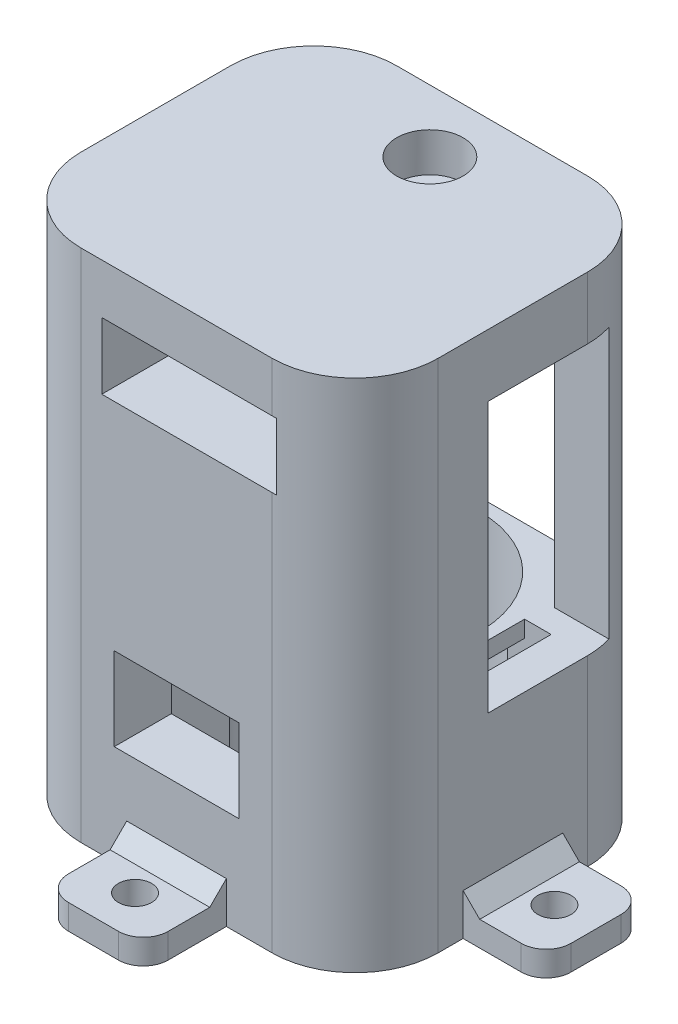
SolidWorks part; units mm, degrees
ref_plane "Plano frontal" through (0, 0, 0) normal (0, 0, 1) x (1, 0, 0)
ref_plane "Plano superior" through (0, 0, 0) normal (0, 1, 0) x (1, 0, 0)
ref_plane "Plano direito" through (0, 0, 0) normal (1, 0, 0) x (0, 0, -1)
sketch "Esboço2" plane through (0, 0, 0) normal (0, 1, 0) x (1, 0, 0)
  line L1 (0, 0) -> (43, 0)
  line L2 (0, 0) -> (0, 38)
  line L3 (0, 38) -> (43, 38)
  line L4 (43, 0) -> (43, 38)
  dimension "D1" = 43
  dimension "D2" = 38
extrude "Base" add sketch "Esboço2" along normal blind 22
sketch "Esboço3" plane through (0, 0, 0) normal (0, 1, 0) x (1, 0, 0)
  line L0 (21.5, -2.1425) -> (21.5, 46.202) construction
  line L1 (-2.8555, 24) -> (47.4642, 24) construction
  line L2 (43, 0) -> (43, 38) construction
  line L3 (43, 38) -> (0, 38) construction
  line L5 (12, 6.876) -> (31, 6.876)
  line L6 (12, 6.876) -> (12, 15.876)
  line L7 (12, 15.876) -> (31, 15.876)
  line L8 (31, 6.876) -> (31, 15.876)
  line L9 (12, 6.876) -> (31, 15.876) construction
  line L10 (12, 15.876) -> (31, 6.876) construction
  circle A0 centre (21.5, 24) radius 12.5
  point P10 (21.5, 11.376)
  point P15 (0, 0)
  point P16 (0, 0)
  dimension "D1" = 25
  dimension "D2" = 21.5
  dimension "D3" = 14
  dimension "D4" = 19
  dimension "D5" = 9
extrude "Corte do encaixe do motor" cut sketch "Esboço3" along normal through all contours A0 L8 L7 L6 | A0 L6 L7 L8 | L6 A0 L8 L5 region at (21.5, 0, -9.99) region at (21.5, 0, -25.3196) region at (21.5, 0, -14.0963)
sketch "Esboço5" plane through (0, 22, 0) normal (0, 1, 0) x (1, 0, 0)
  line L0 (42.9706, 24) -> (-2.5153, 24) construction
  line L1 (21.5, 41.517) -> (21.5, 6.483) construction
  line L3 (4.4, 28) -> (7.6, 28)
  line L4 (4.4, 28) -> (4.4, 20)
  line L5 (4.4, 20) -> (7.6, 20)
  line L6 (7.6, 28) -> (7.6, 20)
  line L7 (4.4, 28) -> (7.6, 20) construction
  line L8 (4.4, 20) -> (7.6, 28) construction
  line L9 (35.4, 28) -> (38.6, 28)
  line L10 (35.4, 28) -> (35.4, 20)
  line L11 (35.4, 20) -> (38.6, 20)
  line L12 (38.6, 28) -> (38.6, 20)
  line L13 (35.4, 28) -> (38.6, 20) construction
  line L14 (35.4, 20) -> (38.6, 28) construction
  point P3 (6, 24)
  point P10 (21.5, 24)
  point P11 (37, 24)
  dimension "D1" = 8
  dimension "D2" = 3.2
  dimension "D3" = 8
  dimension "D4" = 3.2
  dimension "D5" = 15.5
  dimension "D6" = 15.5
extrude "Corte dos parafusos do motor" cut sketch "Esboço5" against normal through all
sketch "Esboço10" plane through (0, 22, 0) normal (0, 1, 0) x (1, 0, 0)
  line L0 (43, 0) -> (43, 38) construction
  line L1 (0, 38) -> (7, 38)
  line L2 (0, 38) -> (0, 31)
  line L3 (0, 31) -> (7, 31)
  line L4 (7, 38) -> (7, 31)
  line L5 (43, 38) -> (36, 38)
  line L6 (43, 38) -> (43, 31)
  line L7 (43, 31) -> (36, 31)
  line L8 (36, 38) -> (36, 31)
  line L9 (0, 0) -> (43, 0)
  line L10 (0, 0) -> (0, 5.5)
  line L11 (0, 5.5) -> (43, 5.5)
  line L12 (43, 0) -> (43, 5.5)
  line L14 (0, 5.5) -> (7, 5.5)
  line L15 (0, 5.5) -> (0, 16)
  line L16 (0, 16) -> (7, 16)
  line L17 (7, 5.5) -> (7, 16)
  line L18 (43, 5.5) -> (36, 5.5)
  line L19 (43, 5.5) -> (43, 16)
  line L20 (43, 16) -> (36, 16)
  line L21 (36, 5.5) -> (36, 16)
  line M13 (31, 6.876) -> (12, 6.876)
  line M15 (0, 0) -> (43, 0)
  line M16 (43, 0) -> (43, 38)
  line M17 (43, 38) -> (0, 38)
  line M18 (0, 38) -> (0, 0)
  dimension "D1" = 5.5
  dimension "D2" = 7
  dimension "D3" = 7
  dimension "D4" = 7
  dimension "D5" = 7
  dimension "D6" = 7
  dimension "D7" = 7
  dimension "D8" = 10.5
  dimension "D9" = 10.5
extrude "Base extendida" add sketch "Esboço10" along normal blind 35 contours L11 M18 M15 M16 M13 | L21 L11 L20 M16 | L8 L7 M17 M16 | L11 L17 L16 M18 | L4 L3 M17 M18 region at (3.5, 22, -34.5) region at (39.5, 22, -34.5) region at (3.5, 22, -10.75) region at (21.5, 22, -2.75) region at (39.5, 22, -10.75)
sketch "Esboço11" plane through (7, 0, 0) normal (1, 0, 0) x (0, 0, -1)
  line L0 (16, 57) -> (16, 47)
  line L1 (16, 57) -> (16, 22) construction
  line L2 (16, 57) -> (5.5, 57)
  line L3 (5.5, 57) -> (16, 57) construction
  line L4 (5.5, 57) -> (5.5, 32.0044)
  line L5 (16, 47) -> (5.5, 32.0044)
  dimension "D1" = 10.5
  dimension "D2" = 35
  dimension "D3" = 10
extrude "Chanfro da base extendida" add sketch "Esboço11" along normal through all
sketch "Esboço12" plane through (0, 0, -16) normal (0, 0, -1) x (-1, 0, 0)
  line L1 (-43, 57) -> (-36, 57)
  line L2 (-43, 57) -> (-43, 54.5)
  line L3 (-43, 54.5) -> (-36, 54.5)
  line L4 (-36, 57) -> (-36, 54.5)
  dimension "D1" = 2.5
  dimension "D2" = 7
extrude "Ponte 1" add sketch "Esboço12" along normal through all
sketch "Esboço13" plane through (0, 0, -16) normal (0, 0, -1) x (-1, 0, 0)
  line L1 (0, 57) -> (-7, 57)
  line L2 (0, 57) -> (0, 54.5)
  line L3 (0, 54.5) -> (-7, 54.5)
  line L4 (-7, 57) -> (-7, 54.5)
  dimension "D1" = 2.5
  dimension "D2" = 7
extrude "Ponte 2" add sketch "Esboço13" along normal through all
sketch "Esboço14" plane through (0, 57, 0) normal (0, 1, 0) x (1, 0, 0)
  line L1 (0, 0) -> (43, 0)
  line L2 (0, 0) -> (0, 38)
  line L3 (0, 38) -> (43, 38)
  line L4 (43, 0) -> (43, 38)
extrude "Telhado" add sketch "Esboço14" along normal blind 5
sketch "Esboço18" plane through (0, 62, 0) normal (0, 1, 0) x (1, 0, 0)
  line L0 (21.5, 37.438) -> (21.5, -2.8891) construction
  line L1 (43, 0) -> (43, 38) construction
  line L2 (43, 38) -> (0, 38) construction
  circle A0 centre (21.5, 30.5) radius 4
  dimension "D2" = 8
  dimension "D3" = 7.5
  dimension "D1" = 21.5
extrude "Furo do Eixo" cut sketch "Esboço18" against normal blind 8
sketch "Esboço23" plane through (0, 57, 0) normal (0, -1, 0) x (1, 0, 0)
  line L0 (36, -30.4716) -> (22.9081, -16)
  line L1 (7, -30.4716) -> (17.2307, -16)
  line L2 (36, -16) -> (36, -30.4716)
  line L3 (36, -38) -> (36, -16) construction
  line L4 (7, -16) -> (36, -16) construction
  line L5 (22.9081, -16) -> (36, -16)
  line L6 (17.2307, -16) -> (7, -16)
  line L7 (7, -38) -> (7, -16) construction
  line L8 (7, -30.4716) -> (7, -16)
  line M3 (36, -38) -> (36, -16)
  line M4 (36, -16) -> (7, -16)
  line M5 (7, -16) -> (7, -38)
extrude "Cama para o telhado" add sketch "Esboço23" along normal blind 0.4 contours M4 M3 | M4 M5 region at (10.4102, 57, -20.8239) region at (31.636, 57, -20.8239)
sketch "Esboço24" plane through (0, 57, 0) normal (0, -1, 0) x (1, 0, 0)
  circle A0 centre (21.5, -30.5) radius 4
extrude "Cama para o furo do eixo" add sketch "Esboço24" against normal blind 0.3
fillet "Filete1" radius 10 1 edges at (43, 31, -38) type face fillet first side face at (43, 31, -19) second side face at (21.5, 39.5, -38)
fillet "Filete2" radius 10 1 edges at (0, 31, -38) type face fillet first side face at (0, 38.25, -23.5) second side face at (18.25, 35.25, -38)
fillet "Filete3" radius 10 1 edges at (0, 31, 0) type face fillet first side face at (0, 34.625, -18) second side face at (21.5, 31, 0)
fillet "Filete4" radius 10 1 edges at (43, 31, 0) type face fillet first side face at (43, 34.625, -18) second side face at (26.5, 31, 0)
sketch "Esboço26" plane through (0, 0, 0) normal (0, 0, 1) x (1, 0, 0)
  line L0 (23, 62.2763) -> (23, -5.3749) construction
  line L1 (43, 62) -> (43, 0) construction
  line L2 (10, 62) -> (33, 62) construction
  line L3 (12.5, 56) -> (33.5, 56)
  line L4 (12.5, 56) -> (12.5, 48)
  line L5 (12.5, 48) -> (33.5, 48)
  line L6 (33.5, 56) -> (33.5, 48)
  line L7 (12.5, 56) -> (33.5, 48) construction
  line L8 (12.5, 48) -> (33.5, 56) construction
  point P5 (23, 52)
  dimension "D1" = 20
  dimension "D2" = 21
  dimension "D3" = 8
  dimension "D4" = 6
extrude "Corte de encaixe do micro switch" cut sketch "Esboço26" against normal blind 20
sketch "Esboço28" plane through (43, 0, 0) normal (1, 0, 0) x (0, 0, -1)
  line L0 (19, -2.6941) -> (19, 10.6017) construction
  line L1 (10, 0) -> (28, 0) construction
  line L2 (13, 0) -> (25, 0)
  line L3 (13, 0) -> (13, 3)
  line L4 (13, 3) -> (25, 3)
  line L5 (25, 0) -> (25, 3)
  dimension "D1" = 19
  dimension "D2" = 12
  dimension "D3" = 3
  dimension "D4" = 6
extrude "Ressalto-extrusão11" add sketch "Esboço28" along normal blind 10
sketch "Esboço29" plane through (0, 3, 0) normal (0, 1, 0) x (1, 0, 0)
  line L0 (43, 25) -> (43, 13) construction
  line L1 (53, 13) -> (43, 13) construction
  circle A0 centre (48, 19) radius 2
  point P4 (43, 19)
  dimension "D1" = 4
  dimension "D2" = 5
  dimension "D3" = 6
extrude "Corte-extrusão2" cut sketch "Esboço29" against normal blind 10
ref_plane "Plano1" through (20, 0, 0) normal (1, 0, 0) x (0, 0, -1)
sketch "Esboço30" plane through (0, 0, 0) normal (0, 0, 1) x (1, 0, 0)
  line L0 (21.5, -2.5658) -> (21.5, 6.588) construction
  line L1 (10, 0) -> (33, 0) construction
  line L2 (15.5, 0) -> (27.5, 0)
  line L3 (15.5, 0) -> (15.5, 3)
  line L4 (15.5, 3) -> (27.5, 3)
  line L5 (27.5, 0) -> (27.5, 3)
  dimension "D1" = 21.5
  dimension "D2" = 3
  dimension "D3" = 12
  dimension "D4" = 6
extrude "Ressalto-extrusão12" add sketch "Esboço30" along normal blind 10
sketch "Esboço31" plane through (0, 3, 0) normal (0, 1, 0) x (1, 0, 0)
  line L0 (27.5, 0) -> (15.5, 0) construction
  line L1 (27.5, -10) -> (27.5, 0) construction
  circle A0 centre (21.5, -5) radius 2
  dimension "D1" = 4
  dimension "D2" = 5
  dimension "D3" = 6
extrude "Corte-extrusão3" cut sketch "Esboço31" against normal blind 10
chamfer "Chanfro1" distance 2 angle 45 1 edges at (43, 3, -19)
chamfer "Chanfro3" distance 2 angle 45 1 edges at (21.5, 3, 0)
fillet "Filete5" radius 3 1 edges at (53, 1.5, -13) type face fillet first side face at (47.4, 2.2, -13) second side face at (53, 1.5, -19)
fillet "Filete6" radius 3 1 edges at (53, 1.5, -25) type face fillet first side face at (47.4, 2.2, -25) second side face at (53, 1.5, -20.5)
fillet "Filete7" radius 3 1 edges at (27.5, 1.5, 10) type face fillet first side face at (21.5, 1.5, 10) second side face at (27.5, 2.2, 4.4)
fillet "Filete8" radius 3 1 edges at (15.5, 1.5, 10) type face fillet first side face at (15.5, 2.2, 4.4) second side face at (20, 1.5, 10)
ref_plane "Plano3" through (0, 0, -17.5) normal (0, 0, 1) x (1, 0, 0)
sketch "Esboço32" plane through (0, 0, 0) normal (0, -1, 0) x (1, 0, 0)
  line L1 (2, -20) -> (41, -20)
  line L2 (2, -20) -> (2, -28)
  line L3 (2, -28) -> (41, -28)
  line L4 (41, -20) -> (41, -28)
  line L5 (2, -20) -> (41, -28) construction
  line L6 (2, -28) -> (41, -20) construction
  point P0 (21.5, -24)
  dimension "D1" = 8
  dimension "D2" = 39
extrude "Corte-extrusão4" cut sketch "Esboço32" against normal blind 20
sketch "Esboço33" plane through (0, 0, 0) normal (0, -1, 0) x (-1, 0, 0)
  line L0 (16.0911, 24) -> (-59.0911, 24) construction
  line L1 (-33, 38) -> (-10, 38) construction
  circle A0 centre (-6, 24) radius 1.5
  circle A1 centre (-37, 24) radius 1.5
  point P4 (-21.5, 24)
  dimension "D2" = 3
  dimension "D3" = 3
  dimension "D4" = 15.5
  dimension "D5" = 15.5
  dimension "D1" = 14
chamfer "Chanfro8" distance 2 angle 45 2 edges at (12, 11, -6.876) (31, 11, -6.876)
chamfer "Chanfro9" distance 2 angle 45 4 edges at (2, 10, -28) (2, 10, -20) (41, 10, -20) (41, 10, -28)
sketch "Esboço35" plane through (0, 0, 0) normal (0, 0, 1) x (1, 0, 0)
  line L0 (21.5, -7.0353) -> (21.5, 32.231) construction
  line L1 (-16.0911, 0) -> (59.0911, 0) construction
  line L2 (14, 22) -> (29, 22)
  line L3 (14, 22) -> (14, 12)
  line L4 (14, 12) -> (29, 12)
  line L5 (29, 22) -> (29, 12)
  line L6 (14, 22) -> (29, 12) construction
  line L7 (14, 12) -> (29, 22) construction
  point P2 (21.5, 17)
  dimension "D1" = 21.5
  dimension "D2" = 15
  dimension "D3" = 10
  dimension "D4" = 17
extrude "Corte para os cabos do motor" cut sketch "Esboço35" against normal blind 20
